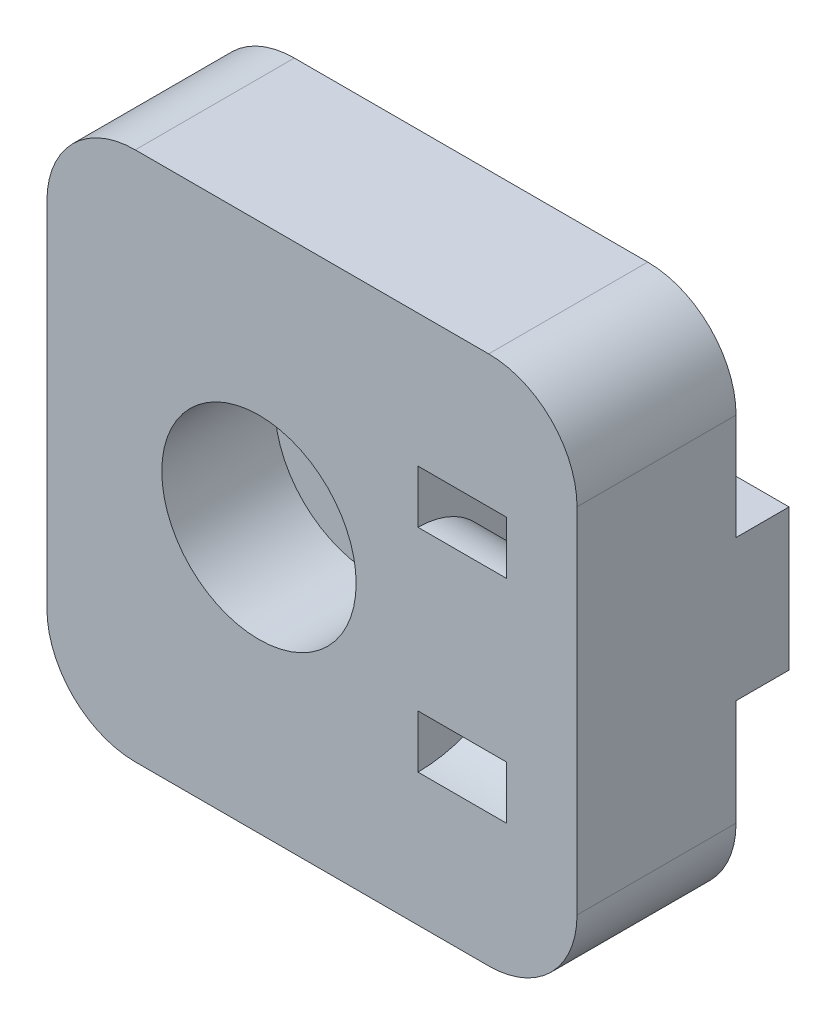
SolidWorks part; units mm, degrees
ref_plane "Přední rovina" through (0, 0, 0) normal (0, 0, 1) x (1, 0, 0)
ref_plane "Horní rovina" through (0, 0, 0) normal (0, 1, 0) x (1, 0, 0)
ref_plane "Pravá rovina" through (0, 0, 0) normal (1, 0, 0) x (0, 0, -1)
sketch "Skica1" plane through (0, 0, 0) normal (0, 0, 1) x (1, 0, 0)
  line L1 (-15, 15) -> (15, 15)
  line L2 (-15, 15) -> (-15, -15)
  line L3 (-15, -15) -> (15, -15)
  line L4 (15, 15) -> (15, -15)
  line L5 (-15, 15) -> (15, -15) construction
  line L6 (-15, -15) -> (15, 15) construction
  point P0 (0, 0)
  dimension "D1" = 30
  dimension "D2" = 30
extrude "Přidat vysunutím1" add sketch "Skica1" along normal blind 9
sketch "Skica2" plane through (0, 0, 9) normal (0, 0, 1) x (1, 0, 0)
  line L0 (-15, 0) -> (15, 0)
  line L1 (-15, 15) -> (-15, -15) construction
  line L2 (15, -15) -> (15, 15) construction
  point P6 (-3, 0)
  dimension "D1" = 12
hole_wizard "Válcové zahloubení pro M6 šrouby s vnitřním šestihranem1" positions "Skica3" profile "Skica4" counterbore size "M6" standard "DIN" end condition through all
sketch "Skica3" plane through (0, 0, 9) normal (0, 0, 1) x (1, 0, 0)
  point P0 (-3, 0)
  point P3 (-24.7725, -8.5167)
sketch "Skica4" plane through (-3, 0, 9) normal (1, 0, 0) x (0, -1, 0)
  line L0 (0, 0) -> (0, 9)
  line L1 (0, 9) -> (3.3, 9)
  line L3 (3.3, 9) -> (3.3, 6.4)
  line L4 (3.3, 6.4) -> (5.5, 6.4)
  line L5 (5.5, 6.4) -> (5.5, 0)
  line L7 (5.5, 0) -> (0, 0)
  line L11 (0, -6.35) -> (0, 107.95) construction
  dimension "Průměr díry skrz" = 6.6
  dimension "Hloubka díry skrz" = 9
  dimension "Průměr válcového zahloubení" = 11
  dimension "Hloubka válcového zahloubení" = 6.4
ref_plane "Rovina1" through (11, 0, 0) normal (1, 0, 0) x (0, 0, -1)
sketch "Tie sketch" plane through (11, 0, 0) normal (1, 0, 0) x (0, 0, -1)
  circle A0 centre (-9, 0) radius 4.5
  circle A1 centre (-9, 0) radius 7.5
  dimension "D1" = 15
  dimension "D2" = 9
extrude "Odebrat vysunutím1" cut sketch "Tie sketch" against normal blind 5
sketch "Skica6" plane through (0, 0, 0) normal (0, 0, -1) x (-1, 0, 0)
  line L0 (0, 15) -> (0, -15)
  line L1 (-15, 15) -> (15, 15) construction
  line L2 (15, -15) -> (-15, -15) construction
  line L3 (15, 15) -> (15, -15) construction
  line L4 (-15, 4) -> (15, 4)
  line L5 (-15, 4) -> (-15, -4)
  line L6 (-15, -4) -> (15, -4)
  line L7 (15, 4) -> (15, -4)
  line L8 (-15, 4) -> (15, -4) construction
  line L9 (-15, -4) -> (15, 4) construction
  circle A0 centre (3, 0) radius 9.5
  point P6 (0, 0)
  line M3 (-15, 15) -> (-15, -15)
  line M5 (15, -15) -> (15, 15)
  dimension "D2" = 19
  dimension "D1" = 8
extrude "Přidat vysunutím2" add sketch "Skica6" along normal blind 3 contours A0 L4 L6 M3 | A0 L6 L4 M5 region at (-13.5934, 0, 0) region at (10.6018, 0, 0)
chamfer "Zkosení1" distance 3 angle 45 1 edges at (6.5, 0, -3)
fillet "Zaoblit1" radius 5 4 edges at (-15, -15, 4.5) (15, -15, 4.5) (15, 15, 4.5) (-15, 15, 4.5)
